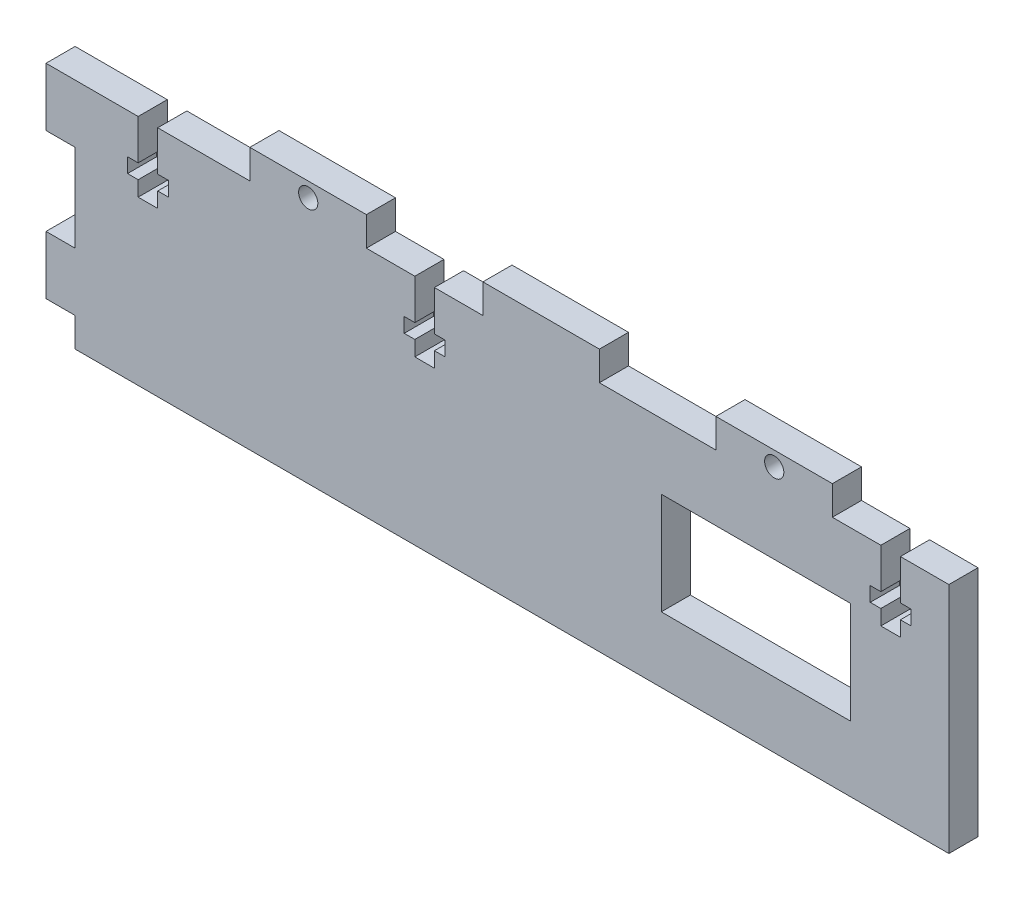
SolidWorks part; units mm, degrees
ref_plane "Front Plane" through (0, 0, 0) normal (0, 0, 1) x (1, 0, 0)
ref_plane "Top Plane" through (0, 0, 0) normal (0, 1, 0) x (1, 0, 0)
ref_plane "Right Plane" through (0, 0, 0) normal (1, 0, 0) x (0, 0, -1)
sketch "Sketch1" plane through (0, 0, 0) normal (0, 0, 1) x (1, 0, 0)
  line L0 (69.2576, 0) -> (-63.1151, 0) construction
  line L1 (42.067, 25.4) -> (-148.433, 25.4)
  line L2 (42.067, 25.4) -> (42.067, -25.4)
  line L3 (42.067, -25.4) -> (-148.433, -25.4)
  line L4 (-148.433, 25.4) -> (-148.433, -25.4)
  line L7 (25.98, 9.3599) -> (20.1295, 9.3599) construction
  line L8 (20.1295, -9.3599) -> (25.98, -9.3599) construction
  line L9 (-148.433, -69.85) -> (-148.433, 54.9538) construction
  line L10 (27.25, 6.27) -> (27.25, 8.0899) construction
  dimension "D1" = 50.8
  dimension "D2" = 14.817
extrude "Boss-Extrude1" add sketch "Sketch1" along normal blind 6.35
sketch "Sketch2" plane through (0, 0, 6.35) normal (0, 0, 1) x (1, 0, 0)
  line L0 (-43.1818, 0) -> (35.1848, 0) construction
  line L1 (-20.6375, 11.1125) -> (20.6375, 11.1125)
  line L2 (-20.6375, 11.1125) -> (-20.6375, -11.1125)
  line L3 (-20.6375, -11.1125) -> (20.6375, -11.1125)
  line L4 (20.6375, 11.1125) -> (20.6375, -11.1125)
  line L5 (-19.6295, 10.033) -> (19.6295, 10.033) construction
  line L6 (19.6295, -10.033) -> (-19.6295, -10.033) construction
  line L7 (0, 18.8234) -> (0, -13.1279) construction
  line L8 (-20.1295, -9.533) -> (-20.1295, 9.533) construction
  line L9 (20.1295, 9.533) -> (20.1295, -9.533) construction
  dimension "D1" = 22.225
  dimension "D2" = 41.275
extrude "Cut-Extrude1" cut sketch "Sketch2" against normal through all
sketch "Sketch3" plane through (0, 25.4, 0) normal (0, 1, 0) x (1, 0, 0)
  line L0 (16.667, 0) -> (16.667, -6.35)
  line L1 (42.067, 0) -> (-148.433, 0) construction
  line L2 (42.067, -6.35) -> (-148.433, -6.35) construction
  line L3 (16.667, -6.35) -> (-8.733, -6.35)
  line L4 (-8.733, -6.35) -> (-8.733, 0)
  line L5 (-8.733, 0) -> (16.667, 0)
  dimension "D1" = 25.4
  dimension "D2" = 25.4
extrude "Boss-Extrude2" add sketch "Sketch3" along normal blind 6.35
pattern_linear "LPattern1" count 3 spacing 50.8 along (-1, 0, 0) of "Boss-Extrude2"
sketch "Sketch4" plane through (-148.433, 0, 0) normal (-1, 0, 0) x (0, 0, 1)
  line L0 (6.35, 25.4) -> (6.35, 12.7)
  line L1 (6.35, 25.4) -> (6.35, -25.4) construction
  line L2 (6.35, 12.7) -> (0, 12.7)
  line L3 (0, 25.4) -> (0, -25.4) construction
  line L4 (0, 12.7) -> (0, 25.4)
  line L5 (0, 25.4) -> (6.35, 25.4)
  dimension "D1" = 12.7
extrude "Boss-Extrude3" add sketch "Sketch4" along normal blind 6.35
pattern_linear "LPattern2" count 2 spacing 31.75 along (0, -1, 0) of "Boss-Extrude3"
sketch "Sketch5" plane through (0, 0, 6.35) normal (0, 0, 1) x (1, 0, 0)
  line L1 (29.367, 25.4) -> (29.367, -8.4837) construction
  line L2 (42.067, 25.4) -> (16.667, 25.4) construction
  line L3 (-72.233, 25.4) -> (-72.233, 3.5007) construction
  line L4 (-59.533, 25.4) -> (-84.933, 25.4) construction
  line L5 (-132.558, 25.4) -> (-132.558, 4.6588) construction
  line L6 (-110.333, 25.4) -> (-154.783, 25.4) construction
  line B0 (31.5006, 25.4) -> (27.2334, 25.4)
  line B1 (27.2334, 13.462) -> (24.922, 13.462)
  line B2 (24.922, 13.462) -> (24.922, 16.637)
  line B3 (24.922, 16.637) -> (27.2334, 16.637)
  line B4 (27.2334, 16.637) -> (27.2334, 25.4)
  line B5 (27.2334, 13.462) -> (27.2334, 10.16)
  line B6 (27.2334, 10.16) -> (31.5006, 10.16)
  line B7 (31.5006, 13.462) -> (31.5006, 10.16)
  line B8 (31.5006, 16.637) -> (31.5006, 25.4)
  line B9 (33.812, 16.637) -> (31.5006, 16.637)
  line B10 (33.812, 13.462) -> (33.812, 16.637)
  line B11 (31.5006, 13.462) -> (33.812, 13.462)
  line B12 (-70.0994, 25.4) -> (-74.3666, 25.4)
  line B13 (-74.3666, 13.462) -> (-76.678, 13.462)
  line B14 (-76.678, 13.462) -> (-76.678, 16.637)
  line B15 (-76.678, 16.637) -> (-74.3666, 16.637)
  line B16 (-74.3666, 16.637) -> (-74.3666, 25.4)
  line B17 (-74.3666, 13.462) -> (-74.3666, 10.16)
  line B18 (-74.3666, 10.16) -> (-70.0994, 10.16)
  line B19 (-70.0994, 13.462) -> (-70.0994, 10.16)
  line B20 (-70.0994, 16.637) -> (-70.0994, 25.4)
  line B21 (-67.788, 16.637) -> (-70.0994, 16.637)
  line B22 (-67.788, 13.462) -> (-67.788, 16.637)
  line B23 (-70.0994, 13.462) -> (-67.788, 13.462)
  line B24 (-130.4244, 25.4) -> (-134.6916, 25.4)
  line B25 (-134.6916, 13.462) -> (-137.003, 13.462)
  line B26 (-137.003, 13.462) -> (-137.003, 16.637)
  line B27 (-137.003, 16.637) -> (-134.6916, 16.637)
  line B28 (-134.6916, 16.637) -> (-134.6916, 25.4)
  line B29 (-134.6916, 13.462) -> (-134.6916, 10.16)
  line B30 (-134.6916, 10.16) -> (-130.4244, 10.16)
  line B31 (-130.4244, 13.462) -> (-130.4244, 10.16)
  line B32 (-130.4244, 16.637) -> (-130.4244, 25.4)
  line B33 (-128.113, 16.637) -> (-130.4244, 16.637)
  line B34 (-128.113, 13.462) -> (-128.113, 16.637)
  line B35 (-130.4244, 13.462) -> (-128.113, 13.462)
sketch_block_instance "TSlot-1"
sketch_block "TSlot" parameters "D1"=3.302, "D2"=3.175
sketch_block_instance "TSlot-4"
sketch_block_instance "TSlot-5"
extrude "Cut-Extrude2" cut sketch "Sketch5" against normal blind 6.35
sketch "Sketch6" plane through (0, 0, 0) normal (0, 0, -1) x (-1, 0, 0)
  line L0 (-1.854, 31.75) -> (-6.1212, 25.4) construction
  line L1 (-16.667, 31.75) -> (8.733, 31.75) construction
  line L2 (-1.854, 31.75) -> (-1.854, 25.4) construction
  line L3 (-6.1212, 31.75) -> (-1.854, 25.4) construction
  line L4 (-6.1212, 25.4) -> (-6.1212, 31.75) construction
  line L5 (99.746, 31.75) -> (95.4788, 25.4) construction
  line L6 (84.933, 31.75) -> (110.333, 31.75) construction
  line L7 (99.746, 31.75) -> (99.746, 25.4) construction
  line L8 (95.4788, 31.75) -> (99.746, 25.4) construction
  line L9 (95.4788, 25.4) -> (95.4788, 31.75) construction
  circle A0 centre (-3.9876, 28.575) radius 2.0955
  circle A1 centre (97.6124, 28.575) radius 2.0955
  dimension "D1" = 4.191
extrude "Cut-Extrude3" cut sketch "Sketch6" against normal through all
